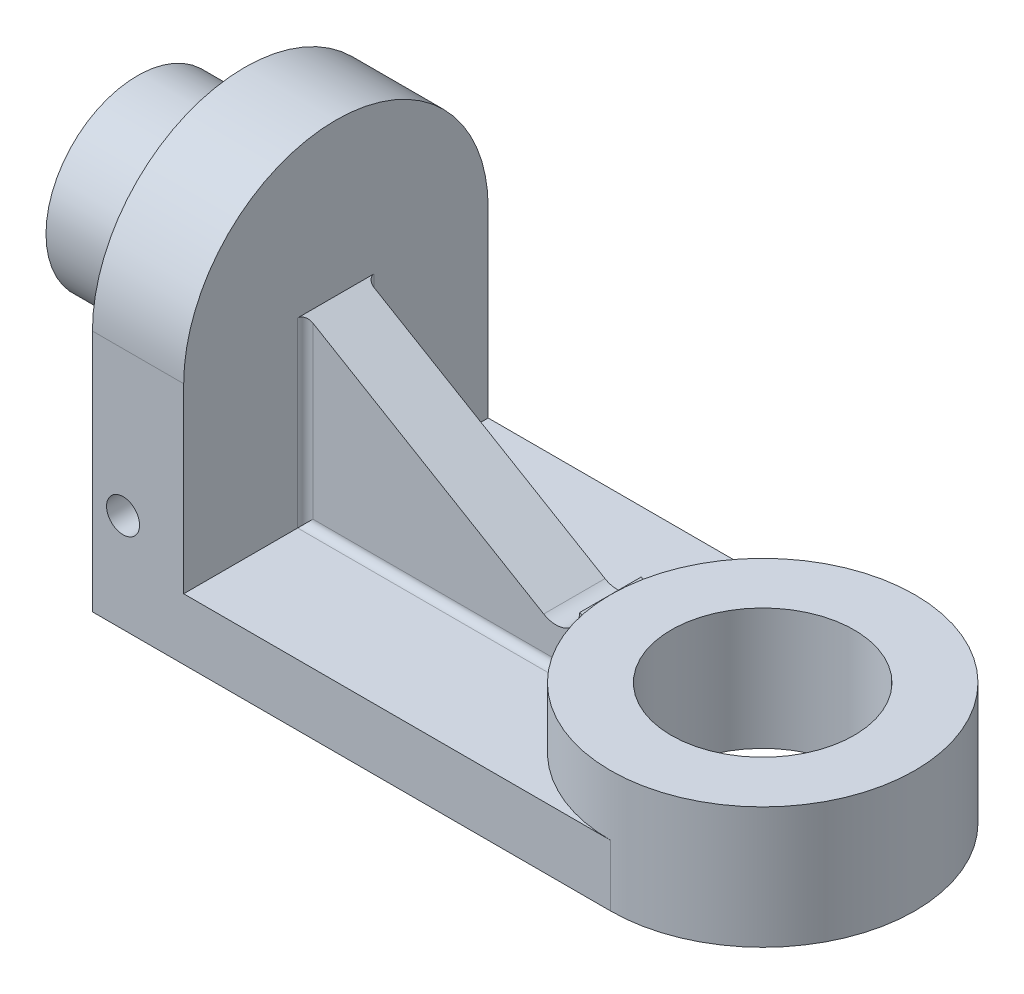
SolidWorks part; units mm, degrees
ref_plane "Front Plane" through (0, 0, 0) normal (0, 0, 1) x (1, 0, 0)
ref_plane "Top Plane" through (0, 0, 0) normal (0, 1, 0) x (1, 0, 0)
ref_plane "Right Plane" through (0, 0, 0) normal (1, 0, 0) x (0, 0, -1)
sketch "Sketch1" plane through (0, 0, 0) normal (0, 1, 0) x (1, 0, 0)
  line L0 (0, 15.9) -> (-54.1, 15.9)
  line L1 (0, -15.9) -> (-54.1, -15.9)
  line L2 (-54.1, -15.9) -> (-54.1, 15.9)
  line L3 (-44.57, 15.9) -> (-44.57, -15.9)
  circle A0 centre (0, 0) radius 9.55
  circle A1 centre (0, 0) radius 15.9
  dimension "D1" = 31.8
  dimension "D2" = 19.1
  dimension "D3" = 54.1
  dimension "D4" = 9.53
extrude "Boss-Extrude1" add sketch "Sketch1" along normal blind 6.4 contours A1 L0 L2 L1 region at (-28.3326, 0, 0)
extrude "Boss-Extrude2" add sketch "Sketch1<3>" along normal blind 12.7 contours A1 A0 region at (10.925, 0, -10.925)
sketch "Sketch1<3>" plane through (0, 0, 0) normal (0, 1, 0) x (1, 0, 0) same geometry as "Sketch1"
extrude "Boss-Extrude3" add sketch "Sketch1<4>" along normal blind 25.4 contours L3 L0 L2 L1 region at (-49.335, 0, 0)
sketch "Sketch1<4>" plane through (0, 0, 0) normal (0, 1, 0) x (1, 0, 0) same geometry as "Sketch1"
sketch "Sketch6" plane through (0, 0, 0) normal (0, 0, 1) x (1, 0, 0)
  line L0 (-15.9, 12.7) -> (-44.57, 25.4)
rib "Rib1" sketch "Sketch6" sketch "Sketch6" thickness 6.4 extrusion direction parallel to sketch draft on no parameters "D1"=6.4
sketch "Sketch7" plane through (0, 0, 0) normal (0, 0, 1) x (1, 0, 0)
  line L2 (-44.57, 25.4) -> (-19.6694, 10.6739)
  line L3 (-44.57, 6.4) -> (-15.5747, 6.4) construction
  line L4 (-44.57, 25.4) -> (-15.9, 12.7)
  arc A0 (-19.6694, 10.6739) -> (-15.9, 12.7) centre (-18.3968, 12.8257) ccw
  dimension "D2" = 5
  dimension "D1" = 30.6
extrude "Cut-Extrude1" cut sketch "Sketch7" against normal through all both and the other way through all
sketch "Sketch8" plane through (-44.57, 0, 0) normal (1, 0, 0) x (0, 0, -1)
  line L0 (3.2, 25.4) -> (-3.2, 25.4) construction
  line L1 (-15.9, 25.4) -> (15.9, 25.4)
  arc A0 (15.9, 25.4) -> (-15.9, 25.4) centre (0, 25.4) ccw
extrude "Boss-Extrude10" add sketch "Sketch8" against normal up to surface (9.53 mm away) up to face at (-54.1, 12.7, 0)
sketch "Sketch9" plane through (-54.1, 0, 0) normal (-1, 0, 0) x (0, 0, 1)
  circle A0 centre (0, 25.4) radius 9.55
  dimension "D1" = 19.1
extrude "Boss-Extrude11" add sketch "Sketch9" along normal blind 11.2
sketch "Sketch10" plane through (-54.1, 0, 0) normal (-1, 0, 0) x (0, 0, 1)
  line L0 (-11.1, 14.2) -> (11.1, 14.2)
  line L1 (11.1, 14.2) -> (11.1, 6.3)
  line L2 (11.1, 6.3) -> (-11.1, 6.3)
  line L3 (-11.1, 6.3) -> (-11.1, 14.2)
  line L4 (15.9, 0) -> (-15.9, 0) construction
  line L5 (-15.9, 25.4) -> (-15.9, 0) construction
  dimension "D1" = 22.2
  dimension "D2" = 7.9
  dimension "D3" = 6.3
  dimension "D4" = 4.8
extrude "Cut-Extrude2" cut sketch "Sketch10" against normal blind 8
sketch "Sketch11" plane through (0, 0, 15.9) normal (0, 0, 1) x (1, 0, 0)
  line L0 (0, 0) -> (-54.1, 0) construction
  line L1 (-54.1, 25.4) -> (-54.1, 0) construction
  circle A0 centre (-50.9, 10.3) radius 1.725
  dimension "D1" = 3.45
  dimension "D2" = 10.3
  dimension "D3" = 3.2
extrude "Cut-Extrude3" cut sketch "Sketch11" against normal through all
sketch "Sketch12" plane through (0, 12.7, 0) normal (0, 1, 0) x (1, 0, 0)
  line L0 (0, 0) -> (11.243, 11.243) construction
  line L1 (0, 0) -> (11.243, -11.243) construction
  line L2 (0, 0) -> (15.9, 0) construction
  circle A0 centre (0, 0) radius 15.9 construction
  point P5 (15.9, 0)
  point P8 (11.243, -11.243)
  point P9 (11.243, 11.243)
  dimension "D1" = 45
  dimension "D2" = 45
fillet "Fillet1" radius 0.8 12 edges at (-46.1, 10.25, 11.1) (-46.1, 6.3, 0) (-46.1, 10.25, -11.1) (-46.1, 14.2, 0) (-50.1, 6.3, 11.1) (-50.1, 14.2, 11.1) (-50.1, 6.3, -11.1) (-50.1, 14.2, -11.1) (-30.0723, 6.4, -3.2) (-30.0723, 6.4, 3.2) (-44.57, 15.9, -3.2) (-44.57, 15.9, 3.2)
